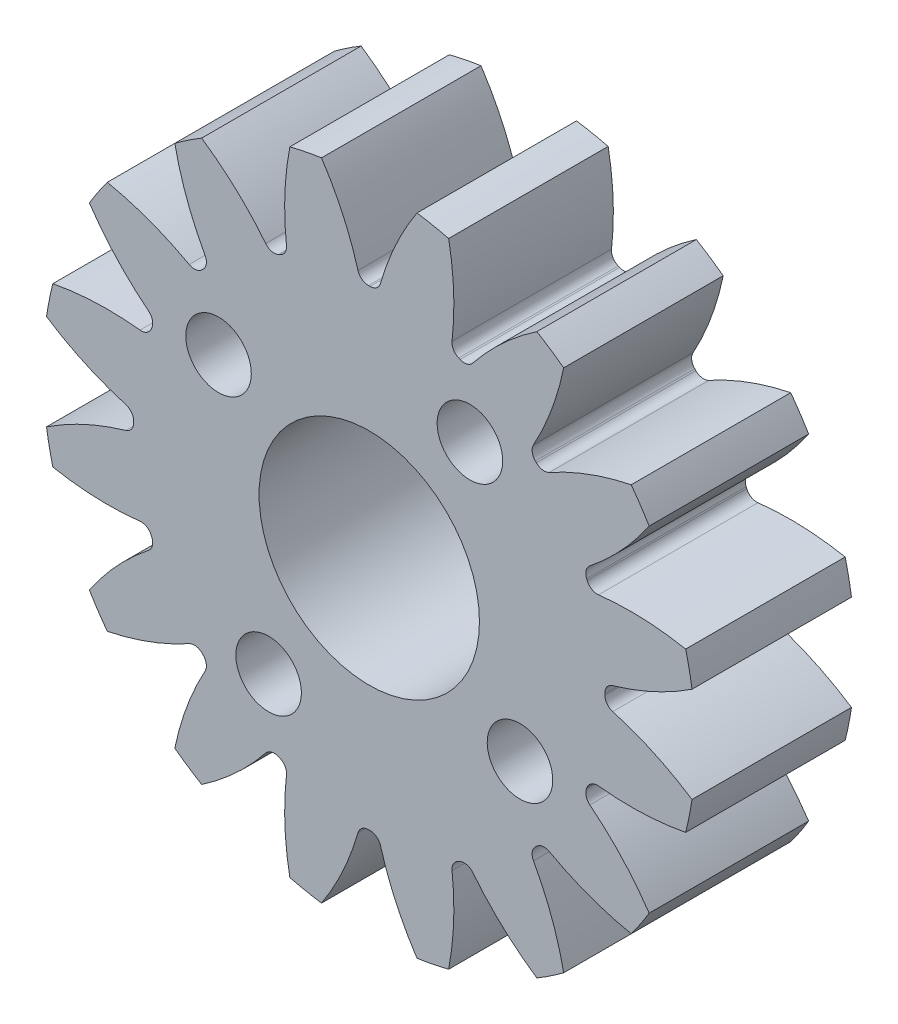
SolidWorks part; units mm, degrees
ref_plane "Front Plane" through (0, 0, 0) normal (0, 0, 1) x (1, 0, 0)
ref_plane "Top Plane" through (0, 0, 0) normal (0, 1, 0) x (1, 0, 0)
ref_plane "Right Plane" through (0, 0, 0) normal (1, 0, 0) x (0, 0, -1)
sketch "Sketch1" plane through (0, 0, 0) normal (0, 0, 1) x (1, 0, 0)
  line L0 (-203.2, 0) -> (203.2, 0) construction
  circle A0 centre (0, 0) radius 14.2875 construction
  circle A1 centre (0, 0) radius 12.7 construction
  circle A2 centre (0, 0) radius 10.3187 construction
  circle A3 centre (0, 0) radius 10.3251 construction
  circle A4 centre (0, 0) radius 6.35 construction
  circle A5 centre (0, 0) radius 10.3187 construction
  dimension "D2" = 1.5875
  dimension "D3" = 3.9688
  dimension "D1" = 3.9688
sketch "Sketch2" plane through (0, 0, 0) normal (1, 0, 0) x (0, 0, -1)
  line L0 (0, 0) -> (-19.05, 0) construction
  line L1 (-19.05, 0) -> (-31.75, 0) construction
  dimension "Overall Width" = 31.75
  dimension "Face Width" = 19.05
sketch "Sketch4" plane through (0, 0, 0) normal (1, 0, 0) x (0, 0, -1)
  line L0 (-31.75, 6.35) -> (-31.75, 10.3251)
  line L1 (-31.75, 10.3251) -> (-19.05, 10.3251)
  line L2 (-19.05, 10.3251) -> (-19.05, 14.2875)
  line L3 (-19.05, 14.2875) -> (0, 14.2875)
  line L4 (0, 14.2875) -> (0, 6.35)
  line L5 (-19.05, 10.3251) -> (-19.05, 0) construction
  line L6 (0, 14.2875) -> (0, -14.2875) construction
  line L7 (-19.05, 10.3251) -> (0, 10.3251) construction
  line L12 (-31.75, 6.35) -> (0, 6.35)
revolve "Revolve1" add sketch "Sketch4" angle 360 about L1
fillet "Fillet2" radius 0.2858 4 edges at (0, 10.3251, 31.75) (0, 10.3251, 19.05) (0, 14.2875, 19.05) (0, 14.2875, 0)
sketch "Sketch7" plane through (0, 0, 19.05) normal (0, 0, 1) x (1, 0, 0)
  line L0 (0, 0) -> (0, 14.2875) construction
  line L1 (1.2448, 12.6388) -> (1.9701, 14.151) construction
  line L3 (2.7874, 14.013) -> (2.4776, 12.456) construction
  line L4 (2.4776, 12.456) -> (2.0131, 10.1205) construction
  line L5 (0, 0) -> (2.0131, 10.1205) construction
  line L6 (1.2448, 12.6388) -> (0, 0) construction
  line L7 (1.2448, 12.6388) -> (1.4004, 14.2187) construction
  line L8 (1.2448, 12.6388) -> (0, 0) construction
  circle A0 centre (0, 0) radius 14.2875 construction
  arc A1 (-0.0331, 10.3187) -> (0.0331, 10.3187) centre (0, 0) cw
  circle A2 centre (0, 0) radius 10.3187 construction
  arc A3 (-1.2448, 12.6388) -> (1.2448, 12.6388) centre (0, 0) cw construction
  circle A4 centre (0, 0) radius 12.7 construction
  arc A5 (3.4772, 13.8579) -> (2.0907, 14.1337) centre (0, 0) ccw construction
  arc A6 (1.2448, 12.6388) -> (3.6866, 12.1531) centre (0, 0) cw construction
  arc A7 (-2.0907, 14.1337) -> (2.0907, 14.1337) centre (0, 0) cw
  arc A8 (0.4923, 10.6631) -> (2.0907, 14.1337) centre (12.6957, 7.1464) cw
  arc A9 (-0.4923, 10.6631) -> (-2.0907, 14.1337) centre (-12.6957, 7.1464) ccw
  arc A10 (-0.0331, 10.3187) -> (-0.4923, 10.6631) centre (-0.0346, 10.795) cw
  arc A11 (0.0331, 10.3187) -> (0.4923, 10.6631) centre (0.0346, 10.795) ccw
  point P26 (-0.3963, 10.3111)
  point P29 (0.3963, 10.3111)
  dimension "D4" = 0.4763
  dimension "D5" = 12.7
  dimension "D3" = 20
  dimension "D1" = 4.9873
  dimension "D2" = 2.4936
extrude "Cut-Extrude2" cut sketch "Sketch7" against normal through all
pattern_circular "CirPattern1" count 16 over 360 about axis through (0, 0, 31.75) along (0, 0, -1) of "Cut-Extrude2"
sketch "Sketch9" [suppressed] plane through (0, 0, 0) normal (0, 0, 1) x (1, 0, 0)
  circle A0 centre (0, 0) radius 10.3187 construction
  circle A1 centre (0, 0) radius 10.3187
ref_plane "Plane1" through (0, 0, 0) normal (0, 0, -1) x (-1, 0, 0)
ref_plane "Plane2" through (0, 0, 31.75) normal (0, 0, 1) x (1, 0, 0)
sketch "Sketch10" plane through (0, 0, 31.75) normal (0, 0, 1) x (1, 0, 0)
  circle A0 centre (0, 0) radius 29.0934
extrude "Cut-Extrude3" cut sketch "Sketch10" against normal blind 15.24
sketch "Sketch11" plane through (0, 0, 0) normal (0, 0, -1) x (-1, 0, 0)
  circle A0 centre (0, 0) radius 20.5552
extrude "Cut-Extrude4" cut sketch "Sketch11" against normal blind 9.525
sketch "Sketch12" plane through (0, 0, 16.51) normal (0, 0, 1) x (1, 0, 0)
  circle A0 centre (0, 0) radius 7.9171
  circle A1 centre (0, 0) radius 4.826
  dimension "D1" = 9.652
extrude "Boss-Extrude1" add sketch "Sketch12" against normal up to surface (6.985 mm away) up to face at (0, 6.35, 9.525)
sketch "Эскиз1" plane through (0, 0, 0) normal (0, 0, -1) x (-1, 0, 0)
  line L0 (0, 0) -> (17.9765, 12.0041) construction
  circle A0 centre (6.601, 4.408) radius 1.4351
  circle A1 centre (4.408, -6.601) radius 1.4351
  circle A2 centre (-6.601, -4.408) radius 1.4351
  circle A3 centre (-4.408, 6.601) radius 1.4351
  dimension "D3" = 2.8702
  dimension "D2" = 7.9375
  dimension "D1" = 4
extrude "Вырез-Вытянуть1" cut sketch "Эскиз1" against normal through all
sketch "Sketch13" plane through (0, 0, 16.51) normal (0, 0, 1) x (1, 0, 0)
  circle A0 centre (-4.408, -6.601) radius 1.4351 construction
  circle A1 centre (-4.408, -6.601) radius 1.4351
  circle A2 centre (6.601, -4.408) radius 1.4351 construction
  circle A3 centre (4.408, 6.601) radius 1.4351 construction
  circle A4 centre (-6.601, 4.408) radius 1.4351 construction
  circle A5 centre (6.601, -4.408) radius 1.4351
  circle A6 centre (4.408, 6.601) radius 1.4351
  circle A7 centre (-6.601, 4.408) radius 1.4351
  circle A8 centre (0, 0) radius 4.826 construction
  circle A9 centre (0, 0) radius 4.826
  arc A96 (-7.3402, -12.2578) -> (-4.5354, -9.663) centre (-14.4641, -1.7439) ccw
  arc A97 (-3.9794, -9.5206) -> (-4.5354, -9.663) centre (-4.1631, -9.96) ccw
  arc A98 (-3.9794, -9.5206) -> (-3.9182, -9.5459) centre (0, 0) ccw
  arc A99 (-3.6258, -10.0398) -> (-3.9182, -9.5459) centre (-4.099, -9.9865) ccw
  arc A100 (-3.6258, -10.0398) -> (-3.4772, -13.8579) centre (8.9945, -11.4608) ccw
  arc A101 (-3.4772, -13.8579) -> (-2.0907, -14.1337) centre (0, 0) ccw
  arc A102 (-2.0907, -14.1337) -> (-0.4923, -10.6631) centre (-12.6957, -7.1464) ccw
  arc A103 (-0.0331, -10.3187) -> (-0.4923, -10.6631) centre (-0.0346, -10.795) ccw
  arc A104 (-0.0331, -10.3187) -> (0.0331, -10.3187) centre (0, 0) ccw
  arc A105 (0.4923, -10.6631) -> (0.0331, -10.3187) centre (0.0346, -10.795) ccw
  arc A106 (0.4923, -10.6631) -> (2.0907, -14.1337) centre (12.6957, -7.1464) ccw
  arc A107 (2.0907, -14.1337) -> (3.4772, -13.8579) centre (0, 0) ccw
  arc A108 (3.4772, -13.8579) -> (3.6258, -10.0398) centre (-8.9945, -11.4608) ccw
  arc A109 (3.9182, -9.5459) -> (3.6258, -10.0398) centre (4.099, -9.9865) ccw
  arc A110 (3.9182, -9.5459) -> (3.9794, -9.5206) centre (0, 0) ccw
  arc A111 (4.5354, -9.663) -> (3.9794, -9.5206) centre (4.1631, -9.96) ccw
  arc A112 (4.5354, -9.663) -> (7.3402, -12.2578) centre (14.4641, -1.7439) ccw
  arc A113 (7.3402, -12.2578) -> (8.5157, -11.4724) centre (0, 0) ccw
  arc A114 (8.5157, -11.4724) -> (7.1918, -7.8881) centre (-3.924, -14.0305) ccw
  arc A115 (7.273, -7.3198) -> (7.1918, -7.8881) centre (7.6087, -7.6577) ccw
  arc A116 (7.273, -7.3198) -> (7.3198, -7.273) centre (0, 0) ccw
  arc A117 (7.8881, -7.1918) -> (7.3198, -7.273) centre (7.6577, -7.6087) ccw
  arc A118 (7.8881, -7.1918) -> (11.4724, -8.5157) centre (14.0305, 3.924) ccw
  arc A119 (11.4724, -8.5157) -> (12.2578, -7.3402) centre (0, 0) ccw
  arc A120 (12.2578, -7.3402) -> (9.663, -4.5354) centre (1.7439, -14.4641) ccw
  arc A121 (9.5206, -3.9794) -> (9.663, -4.5354) centre (9.96, -4.1631) ccw
  arc A122 (9.5206, -3.9794) -> (9.5459, -3.9182) centre (0, 0) ccw
  arc A123 (10.0398, -3.6258) -> (9.5459, -3.9182) centre (9.9865, -4.099) ccw
  arc A124 (10.0398, -3.6258) -> (13.8579, -3.4772) centre (11.4608, 8.9945) ccw
  arc A125 (13.8579, -3.4772) -> (14.1337, -2.0907) centre (0, 0) ccw
  arc A126 (14.1337, -2.0907) -> (10.6631, -0.4923) centre (7.1464, -12.6957) ccw
  arc A127 (10.3187, -0.0331) -> (10.6631, -0.4923) centre (10.795, -0.0346) ccw
  arc A128 (10.3187, -0.0331) -> (10.3187, 0.0331) centre (0, 0) ccw
  arc A129 (10.6631, 0.4923) -> (10.3187, 0.0331) centre (10.795, 0.0346) ccw
  arc A130 (10.6631, 0.4923) -> (14.1337, 2.0907) centre (7.1464, 12.6957) ccw
  arc A131 (14.1337, 2.0907) -> (13.8579, 3.4772) centre (0, 0) ccw
  arc A132 (13.8579, 3.4772) -> (10.0398, 3.6258) centre (11.4608, -8.9945) ccw
  arc A133 (9.5459, 3.9182) -> (10.0398, 3.6258) centre (9.9865, 4.099) ccw
  arc A134 (9.5459, 3.9182) -> (9.5206, 3.9794) centre (0, 0) ccw
  arc A135 (9.663, 4.5354) -> (9.5206, 3.9794) centre (9.96, 4.1631) ccw
  arc A136 (9.663, 4.5354) -> (12.2578, 7.3402) centre (1.7439, 14.4641) ccw
  arc A137 (12.2578, 7.3402) -> (11.4724, 8.5157) centre (0, 0) ccw
  arc A138 (11.4724, 8.5157) -> (7.8881, 7.1918) centre (14.0305, -3.924) ccw
  arc A139 (7.3198, 7.273) -> (7.8881, 7.1918) centre (7.6577, 7.6087) ccw
  arc A140 (7.3198, 7.273) -> (7.273, 7.3198) centre (0, 0) ccw
  arc A141 (7.1918, 7.8881) -> (7.273, 7.3198) centre (7.6087, 7.6577) ccw
  arc A142 (7.1918, 7.8881) -> (8.5157, 11.4724) centre (-3.924, 14.0305) ccw
  arc A143 (8.5157, 11.4724) -> (7.3402, 12.2578) centre (0, 0) ccw
  arc A144 (7.3402, 12.2578) -> (4.5354, 9.663) centre (14.4641, 1.7439) ccw
  arc A145 (3.9794, 9.5206) -> (4.5354, 9.663) centre (4.1631, 9.96) ccw
  arc A146 (3.9794, 9.5206) -> (3.9182, 9.5459) centre (0, 0) ccw
  arc A147 (3.6258, 10.0398) -> (3.9182, 9.5459) centre (4.099, 9.9865) ccw
  arc A148 (3.6258, 10.0398) -> (3.4772, 13.8579) centre (-8.9945, 11.4608) ccw
  arc A149 (3.4772, 13.8579) -> (2.0907, 14.1337) centre (0, 0) ccw
  arc A150 (2.0907, 14.1337) -> (0.4923, 10.6631) centre (12.6957, 7.1464) ccw
  arc A151 (0.0331, 10.3187) -> (0.4923, 10.6631) centre (0.0346, 10.795) ccw
  arc A152 (0.0331, 10.3187) -> (-0.0331, 10.3187) centre (0, 0) ccw
  arc A153 (-0.4923, 10.6631) -> (-0.0331, 10.3187) centre (-0.0346, 10.795) ccw
  arc A154 (-0.4923, 10.6631) -> (-2.0907, 14.1337) centre (-12.6957, 7.1464) ccw
  arc A155 (-2.0907, 14.1337) -> (-3.4772, 13.8579) centre (0, 0) ccw
  arc A156 (-3.4772, 13.8579) -> (-3.6258, 10.0398) centre (8.9945, 11.4608) ccw
  arc A157 (-3.9182, 9.5459) -> (-3.6258, 10.0398) centre (-4.099, 9.9865) ccw
  arc A158 (-3.9182, 9.5459) -> (-3.9794, 9.5206) centre (0, 0) ccw
  arc A159 (-4.5354, 9.663) -> (-3.9794, 9.5206) centre (-4.1631, 9.96) ccw
  arc A160 (-4.5354, 9.663) -> (-7.3402, 12.2578) centre (-14.4641, 1.7439) ccw
  arc A161 (-7.3402, 12.2578) -> (-8.5157, 11.4724) centre (0, 0) ccw
  arc A162 (-8.5157, 11.4724) -> (-7.1918, 7.8881) centre (3.924, 14.0305) ccw
  arc A163 (-7.273, 7.3198) -> (-7.1918, 7.8881) centre (-7.6087, 7.6577) ccw
  arc A164 (-7.273, 7.3198) -> (-7.3198, 7.273) centre (0, 0) ccw
  arc A165 (-7.8881, 7.1918) -> (-7.3198, 7.273) centre (-7.6577, 7.6087) ccw
  arc A166 (-7.8881, 7.1918) -> (-11.4724, 8.5157) centre (-14.0305, -3.924) ccw
  arc A167 (-11.4724, 8.5157) -> (-12.2578, 7.3402) centre (0, 0) ccw
  arc A168 (-12.2578, 7.3402) -> (-9.663, 4.5354) centre (-1.7439, 14.4641) ccw
  arc A169 (-9.5206, 3.9794) -> (-9.663, 4.5354) centre (-9.96, 4.1631) ccw
  arc A170 (-9.5206, 3.9794) -> (-9.5459, 3.9182) centre (0, 0) ccw
  arc A171 (-10.0398, 3.6258) -> (-9.5459, 3.9182) centre (-9.9865, 4.099) ccw
  arc A172 (-10.0398, 3.6258) -> (-13.8579, 3.4772) centre (-11.4608, -8.9945) ccw
  arc A173 (-13.8579, 3.4772) -> (-14.1337, 2.0907) centre (0, 0) ccw
  arc A174 (-14.1337, 2.0907) -> (-10.6631, 0.4923) centre (-7.1464, 12.6957) ccw
  arc A175 (-10.3187, 0.0331) -> (-10.6631, 0.4923) centre (-10.795, 0.0346) ccw
  arc A176 (-10.3187, 0.0331) -> (-10.3187, -0.0331) centre (0, 0) ccw
  arc A177 (-10.6631, -0.4923) -> (-10.3187, -0.0331) centre (-10.795, -0.0346) ccw
  arc A178 (-10.6631, -0.4923) -> (-14.1337, -2.0907) centre (-7.1464, -12.6957) ccw
  arc A179 (-14.1337, -2.0907) -> (-13.8579, -3.4772) centre (0, 0) ccw
  arc A180 (-13.8579, -3.4772) -> (-10.0398, -3.6258) centre (-11.4608, 8.9945) ccw
  arc A181 (-9.5459, -3.9182) -> (-10.0398, -3.6258) centre (-9.9865, -4.099) ccw
  arc A182 (-9.5459, -3.9182) -> (-9.5206, -3.9794) centre (0, 0) ccw
  arc A183 (-9.663, -4.5354) -> (-9.5206, -3.9794) centre (-9.96, -4.1631) ccw
  arc A184 (-9.663, -4.5354) -> (-12.2578, -7.3402) centre (-1.7439, -14.4641) ccw
  arc A185 (-12.2578, -7.3402) -> (-11.4724, -8.5157) centre (0, 0) ccw
  arc A186 (-11.4724, -8.5157) -> (-7.8881, -7.1918) centre (-14.0305, 3.924) ccw
  arc A187 (-7.3198, -7.273) -> (-7.8881, -7.1918) centre (-7.6577, -7.6087) ccw
  arc A188 (-7.3198, -7.273) -> (-7.273, -7.3198) centre (0, 0) ccw
  arc A189 (-7.1918, -7.8881) -> (-7.273, -7.3198) centre (-7.6087, -7.6577) ccw
  arc A190 (-7.1918, -7.8881) -> (-8.5157, -11.4724) centre (3.924, -14.0305) ccw
  arc A191 (-8.5157, -11.4724) -> (-7.3402, -12.2578) centre (0, 0) ccw
  arc A192 (-7.3402, -12.2578) -> (-4.5354, -9.663) centre (-14.4641, -1.7439) ccw
  arc A193 (-3.9794, -9.5206) -> (-4.5354, -9.663) centre (-4.1631, -9.96) ccw
  arc A194 (-3.9794, -9.5206) -> (-3.9182, -9.5459) centre (0, 0) ccw
  arc A195 (-3.6258, -10.0398) -> (-3.9182, -9.5459) centre (-4.099, -9.9865) ccw
  arc A196 (-3.6258, -10.0398) -> (-3.4772, -13.8579) centre (8.9945, -11.4608) ccw
  arc A197 (-3.4772, -13.8579) -> (-2.0907, -14.1337) centre (0, 0) ccw
  arc A198 (-2.0907, -14.1337) -> (-0.4923, -10.6631) centre (-12.6957, -7.1464) ccw
  arc A199 (-0.0331, -10.3187) -> (-0.4923, -10.6631) centre (-0.0346, -10.795) ccw
  arc A200 (-0.0331, -10.3187) -> (0.0331, -10.3187) centre (0, 0) ccw
  arc A201 (0.4923, -10.6631) -> (0.0331, -10.3187) centre (0.0346, -10.795) ccw
  arc A202 (0.4923, -10.6631) -> (2.0907, -14.1337) centre (12.6957, -7.1464) ccw
  arc A203 (2.0907, -14.1337) -> (3.4772, -13.8579) centre (0, 0) ccw
  arc A204 (3.4772, -13.8579) -> (3.6258, -10.0398) centre (-8.9945, -11.4608) ccw
  arc A205 (3.9182, -9.5459) -> (3.6258, -10.0398) centre (4.099, -9.9865) ccw
  arc A206 (3.9182, -9.5459) -> (3.9794, -9.5206) centre (0, 0) ccw
  arc A207 (4.5354, -9.663) -> (3.9794, -9.5206) centre (4.1631, -9.96) ccw
  arc A208 (4.5354, -9.663) -> (7.3402, -12.2578) centre (14.4641, -1.7439) ccw
  arc A209 (7.3402, -12.2578) -> (8.5157, -11.4724) centre (0, 0) ccw
  arc A210 (8.5157, -11.4724) -> (7.1918, -7.8881) centre (-3.924, -14.0305) ccw
  arc A211 (7.273, -7.3198) -> (7.1918, -7.8881) centre (7.6087, -7.6577) ccw
  arc A212 (7.273, -7.3198) -> (7.3198, -7.273) centre (0, 0) ccw
  arc A213 (7.8881, -7.1918) -> (7.3198, -7.273) centre (7.6577, -7.6087) ccw
  arc A214 (7.8881, -7.1918) -> (11.4724, -8.5157) centre (14.0305, 3.924) ccw
  arc A215 (11.4724, -8.5157) -> (12.2578, -7.3402) centre (0, 0) ccw
  arc A216 (12.2578, -7.3402) -> (9.663, -4.5354) centre (1.7439, -14.4641) ccw
  arc A217 (9.5206, -3.9794) -> (9.663, -4.5354) centre (9.96, -4.1631) ccw
  arc A218 (9.5206, -3.9794) -> (9.5459, -3.9182) centre (0, 0) ccw
  arc A219 (10.0398, -3.6258) -> (9.5459, -3.9182) centre (9.9865, -4.099) ccw
  arc A220 (10.0398, -3.6258) -> (13.8579, -3.4772) centre (11.4608, 8.9945) ccw
  arc A221 (13.8579, -3.4772) -> (14.1337, -2.0907) centre (0, 0) ccw
  arc A222 (14.1337, -2.0907) -> (10.6631, -0.4923) centre (7.1464, -12.6957) ccw
  arc A223 (10.3187, -0.0331) -> (10.6631, -0.4923) centre (10.795, -0.0346) ccw
  arc A224 (10.3187, -0.0331) -> (10.3187, 0.0331) centre (0, 0) ccw
  arc A225 (10.6631, 0.4923) -> (10.3187, 0.0331) centre (10.795, 0.0346) ccw
  arc A226 (10.6631, 0.4923) -> (14.1337, 2.0907) centre (7.1464, 12.6957) ccw
  arc A227 (14.1337, 2.0907) -> (13.8579, 3.4772) centre (0, 0) ccw
  arc A228 (13.8579, 3.4772) -> (10.0398, 3.6258) centre (11.4608, -8.9945) ccw
  arc A229 (9.5459, 3.9182) -> (10.0398, 3.6258) centre (9.9865, 4.099) ccw
  arc A230 (9.5459, 3.9182) -> (9.5206, 3.9794) centre (0, 0) ccw
  arc A231 (9.663, 4.5354) -> (9.5206, 3.9794) centre (9.96, 4.1631) ccw
  arc A232 (9.663, 4.5354) -> (12.2578, 7.3402) centre (1.7439, 14.4641) ccw
  arc A233 (12.2578, 7.3402) -> (11.4724, 8.5157) centre (0, 0) ccw
  arc A234 (11.4724, 8.5157) -> (7.8881, 7.1918) centre (14.0305, -3.924) ccw
  arc A235 (7.3198, 7.273) -> (7.8881, 7.1918) centre (7.6577, 7.6087) ccw
  arc A236 (7.3198, 7.273) -> (7.273, 7.3198) centre (0, 0) ccw
  arc A237 (7.1918, 7.8881) -> (7.273, 7.3198) centre (7.6087, 7.6577) ccw
  arc A238 (7.1918, 7.8881) -> (8.5157, 11.4724) centre (-3.924, 14.0305) ccw
  arc A239 (8.5157, 11.4724) -> (7.3402, 12.2578) centre (0, 0) ccw
  arc A240 (7.3402, 12.2578) -> (4.5354, 9.663) centre (14.4641, 1.7439) ccw
  arc A241 (3.9794, 9.5206) -> (4.5354, 9.663) centre (4.1631, 9.96) ccw
  arc A242 (3.9794, 9.5206) -> (3.9182, 9.5459) centre (0, 0) ccw
  arc A243 (3.6258, 10.0398) -> (3.9182, 9.5459) centre (4.099, 9.9865) ccw
  arc A244 (3.6258, 10.0398) -> (3.4772, 13.8579) centre (-8.9945, 11.4608) ccw
  arc A245 (3.4772, 13.8579) -> (2.0907, 14.1337) centre (0, 0) ccw
  arc A246 (2.0907, 14.1337) -> (0.4923, 10.6631) centre (12.6957, 7.1464) ccw
  arc A247 (0.0331, 10.3187) -> (0.4923, 10.6631) centre (0.0346, 10.795) ccw
  arc A248 (0.0331, 10.3187) -> (-0.0331, 10.3187) centre (0, 0) ccw
  arc A249 (-0.4923, 10.6631) -> (-0.0331, 10.3187) centre (-0.0346, 10.795) ccw
  arc A250 (-0.4923, 10.6631) -> (-2.0907, 14.1337) centre (-12.6957, 7.1464) ccw
  arc A251 (-2.0907, 14.1337) -> (-3.4772, 13.8579) centre (0, 0) ccw
  arc A252 (-3.4772, 13.8579) -> (-3.6258, 10.0398) centre (8.9945, 11.4608) ccw
  arc A253 (-3.9182, 9.5459) -> (-3.6258, 10.0398) centre (-4.099, 9.9865) ccw
  arc A254 (-3.9182, 9.5459) -> (-3.9794, 9.5206) centre (0, 0) ccw
  arc A255 (-4.5354, 9.663) -> (-3.9794, 9.5206) centre (-4.1631, 9.96) ccw
  arc A256 (-4.5354, 9.663) -> (-7.3402, 12.2578) centre (-14.4641, 1.7439) ccw
  arc A257 (-7.3402, 12.2578) -> (-8.5157, 11.4724) centre (0, 0) ccw
  arc A258 (-8.5157, 11.4724) -> (-7.1918, 7.8881) centre (3.924, 14.0305) ccw
  arc A259 (-7.273, 7.3198) -> (-7.1918, 7.8881) centre (-7.6087, 7.6577) ccw
  arc A260 (-7.273, 7.3198) -> (-7.3198, 7.273) centre (0, 0) ccw
  arc A261 (-7.8881, 7.1918) -> (-7.3198, 7.273) centre (-7.6577, 7.6087) ccw
  arc A262 (-7.8881, 7.1918) -> (-11.4724, 8.5157) centre (-14.0305, -3.924) ccw
  arc A263 (-11.4724, 8.5157) -> (-12.2578, 7.3402) centre (0, 0) ccw
  arc A264 (-12.2578, 7.3402) -> (-9.663, 4.5354) centre (-1.7439, 14.4641) ccw
  arc A265 (-9.5206, 3.9794) -> (-9.663, 4.5354) centre (-9.96, 4.1631) ccw
  arc A266 (-9.5206, 3.9794) -> (-9.5459, 3.9182) centre (0, 0) ccw
  arc A267 (-10.0398, 3.6258) -> (-9.5459, 3.9182) centre (-9.9865, 4.099) ccw
  arc A268 (-10.0398, 3.6258) -> (-13.8579, 3.4772) centre (-11.4608, -8.9945) ccw
  arc A269 (-13.8579, 3.4772) -> (-14.1337, 2.0907) centre (0, 0) ccw
  arc A270 (-14.1337, 2.0907) -> (-10.6631, 0.4923) centre (-7.1464, 12.6957) ccw
  arc A271 (-10.3187, 0.0331) -> (-10.6631, 0.4923) centre (-10.795, 0.0346) ccw
  arc A272 (-10.3187, 0.0331) -> (-10.3187, -0.0331) centre (0, 0) ccw
  arc A273 (-10.6631, -0.4923) -> (-10.3187, -0.0331) centre (-10.795, -0.0346) ccw
  arc A274 (-10.6631, -0.4923) -> (-14.1337, -2.0907) centre (-7.1464, -12.6957) ccw
  arc A275 (-14.1337, -2.0907) -> (-13.8579, -3.4772) centre (0, 0) ccw
  arc A276 (-13.8579, -3.4772) -> (-10.0398, -3.6258) centre (-11.4608, 8.9945) ccw
  arc A277 (-9.5459, -3.9182) -> (-10.0398, -3.6258) centre (-9.9865, -4.099) ccw
  arc A278 (-9.5459, -3.9182) -> (-9.5206, -3.9794) centre (0, 0) ccw
  arc A279 (-9.663, -4.5354) -> (-9.5206, -3.9794) centre (-9.96, -4.1631) ccw
  arc A280 (-9.663, -4.5354) -> (-12.2578, -7.3402) centre (-1.7439, -14.4641) ccw
  arc A281 (-12.2578, -7.3402) -> (-11.4724, -8.5157) centre (0, 0) ccw
  arc A282 (-11.4724, -8.5157) -> (-7.8881, -7.1918) centre (-14.0305, 3.924) ccw
  arc A283 (-7.3198, -7.273) -> (-7.8881, -7.1918) centre (-7.6577, -7.6087) ccw
  arc A284 (-7.3198, -7.273) -> (-7.273, -7.3198) centre (0, 0) ccw
  arc A285 (-7.1918, -7.8881) -> (-7.273, -7.3198) centre (-7.6087, -7.6577) ccw
  arc A286 (-7.1918, -7.8881) -> (-8.5157, -11.4724) centre (3.924, -14.0305) ccw
  arc A287 (-8.5157, -11.4724) -> (-7.3402, -12.2578) centre (0, 0) ccw
  dimension "D1" = 0
equation "\"D1@Sketch1\"=2.5*(\"Pitch Dia.@Sketch1\"/\"Number of Teeth@Sketch1\")"
equation "\"D1@CirPattern1\"=\"Number of Teeth@Sketch1\""
equation "\"D1@Fillet2\"=\"OD@Sketch1\"*.01"
equation "\"D1@Sketch7\"=3.14159*(\"Pitch Dia.@Sketch1\"/\"Number of Teeth@Sketch1\")"
equation "\"D2@Sketch7\"=\"D1@Sketch7\"/2"
equation "\"D4@Sketch7\"=\"D1@Sketch7\"*.0955"
equation "\"D5@Sketch7\"=\"Pitch Dia.@Sketch1\"/2"
